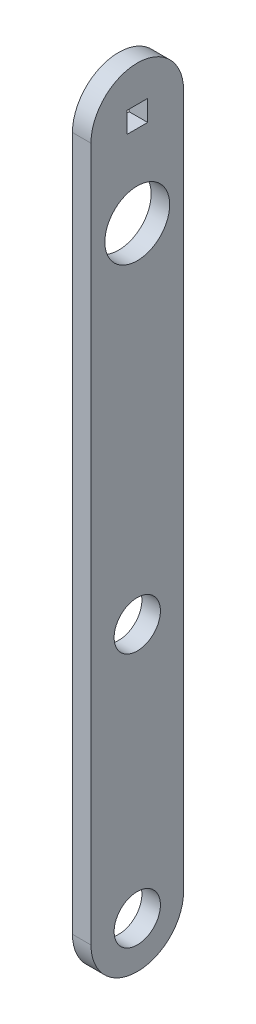
SolidWorks part; units mm, degrees
ref_plane "Front Plane" through (0, 0, 0) normal (0, 0, 1) x (1, 0, 0)
ref_plane "Top Plane" through (0, 0, 0) normal (0, 1, 0) x (1, 0, 0)
ref_plane "Right Plane" through (0, 0, 0) normal (1, 0, 0) x (0, 0, -1)
sketch "Sketch2" plane through (0, 0, 0) normal (1, 0, 0) x (0, 0, -1)
  line L0 (-20, 0) -> (20, 0) construction
  line L1 (-20, 40) -> (-20, -260)
  line L2 (20, 40) -> (20, -260)
  line L3 (0, 0) -> (0, 40) construction
  line L4 (20, 40) -> (-20, 40) construction
  line L5 (-4.5, 35.5) -> (4.5, 35.5)
  line L6 (-4.5, 35.5) -> (-4.5, 44.5)
  line L7 (-4.5, 44.5) -> (4.5, 44.5)
  line L8 (4.5, 35.5) -> (4.5, 44.5)
  line L9 (-4.5, 35.5) -> (4.5, 44.5) construction
  line L10 (-4.5, 44.5) -> (4.5, 35.5) construction
  line L11 (-20, -260) -> (20, -260) construction
  line L12 (0, 0) -> (0, -150) construction
  circle A0 centre (0, 0) radius 14
  arc A1 (-20, 40) -> (20, 40) centre (0, 40) cw
  circle A2 centre (0, -150) radius 10
  arc A3 (-20, -260) -> (20, -260) centre (0, -260) ccw
  circle A4 centre (0, -260) radius 10
  dimension "D1" = 28
  dimension "D7" = 20
  dimension "D8" = 20
  dimension "D2" = 40
  dimension "D3" = 40
  dimension "D4" = 9
  dimension "D5" = 300
  dimension "D6" = 150
extrude "Boss-Extrude1" add sketch "Sketch2" along normal blind 4 and the other way blind 4 contours L1 A3 L2 A1 L8 L5 L6 L7 A0 A2 region at (0, -111.6924, 0)
sketch "Sketch3" plane through (0, 0, 0) normal (0, 0, 1) x (1, 0, 0)
  line L0 (-46.8798, 0) -> (46.8798, 0) construction
